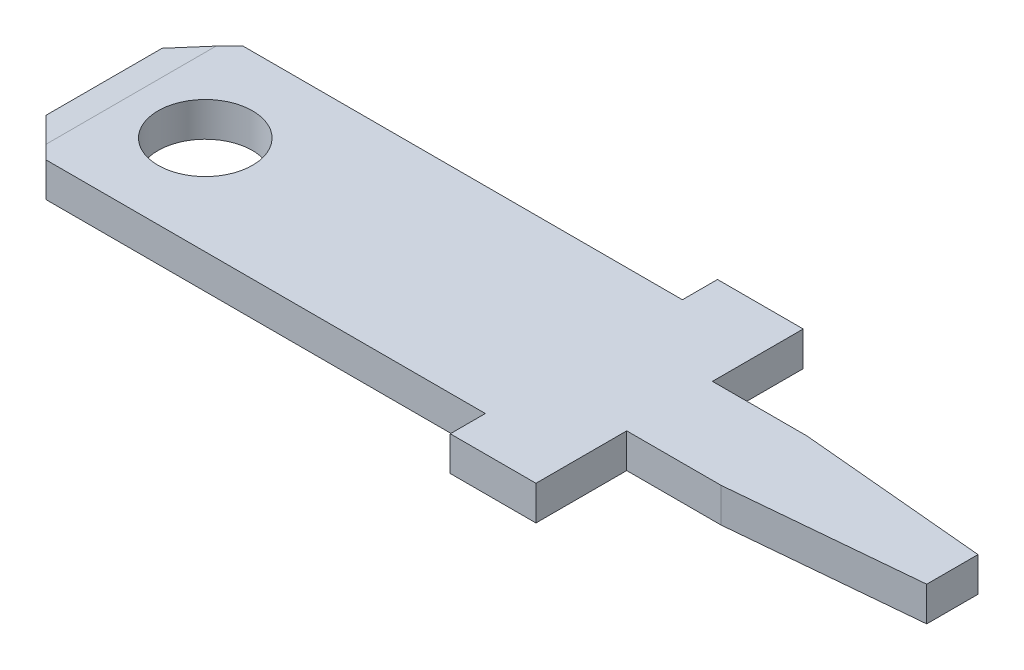
SolidWorks part; units mm, degrees
material "Pure Gold"
ref_plane "Front Plane" through (0, 0, 0) normal (0, 0, 1) x (1, 0, 0)
ref_plane "Top Plane" through (0, 0, 0) normal (0, 1, 0) x (1, 0, 0)
ref_plane "Right Plane" through (0, 0, 0) normal (1, 0, 0) x (0, 0, -1)
sketch "Sketch1" plane through (0, 0, 0) normal (0, 1, 0) x (1, 0, 0)
  line L0 (0, 1.98) -> (-1.27, 1.98)
  line L1 (0, -55) -> (0, 55) construction
  line L2 (-1.27, 1.98) -> (-1.27, 1.46)
  line L3 (-1.27, 1.46) -> (-7.78, 1.46)
  line L4 (-7.78, 1.46) -> (-8.38, 0.86)
  line L5 (-8.38, 0.86) -> (-8.38, 0)
  line L6 (-55, 0) -> (55, 0) construction
  line L7 (-8.38, 0) -> (4.19, 0)
  line L8 (4.19, 0) -> (4.19, 0.38)
  line L9 (4.19, 0.38) -> (1.4, 0.635)
  line L10 (1.4, 0.635) -> (0, 0.635)
  line L11 (0, 0.635) -> (0, 1.98)
  dimension "D1" = 1.27
  dimension "D2" = 7.11
  dimension "D3" = 1.46
  dimension "D4" = 1.98
  dimension "D5" = 45
  dimension "D6" = 0.6
  dimension "D7" = 0.635
  dimension "D8" = 0.38
  dimension "D9" = 1.4
  dimension "D10" = 4.19
extrude "Boss-Extrude1" add sketch "Sketch1" along normal mid plane 0.51
mirror "Mirror1" about plane through (-8.38, 0.255, 0) normal (0, 0, -1) of "Boss-Extrude1"
sketch "Sketch2" plane through (0, 0.255, 0) normal (0, 1, 0) x (1, 0, 0)
  line L0 (-1.27, 1.98) -> (-1.27, 1.46) construction
  circle A0 centre (-6.88, 0) radius 0.7
  dimension "D1" = 1.4
  dimension "D2" = 5.61
extrude "Cut-Extrude1" cut sketch "Sketch2" against normal through all
chamfer "Chamfer1" distance 0.4 angle 4 2 edges at (-8.38, -0.255, 0) (-8.38, 0.255, 0) first distance on face at (-6.88, -0.255, 0.7) first distance on face at (-6.88, 0.255, 0.7)
ref_axis "Centre Axis" through (4.8185, 0, 0) along (-1, 0, 0)
